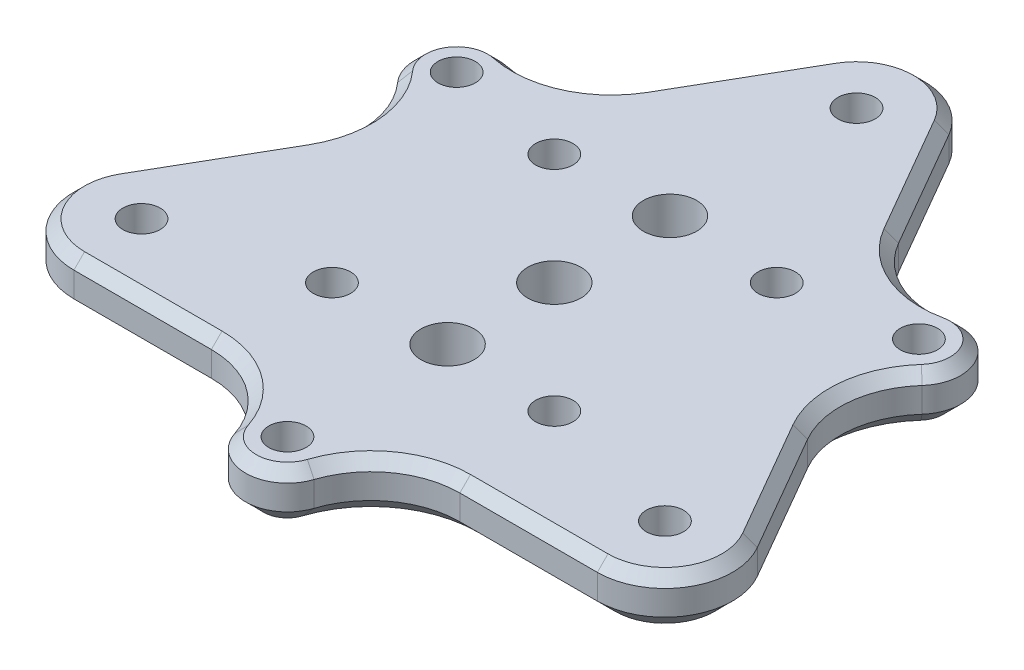
SolidWorks part; units mm, degrees
material "2014 合金"
ref_plane "正面" through (0, 0, 0) normal (0, 0, 1) x (1, 0, 0)
ref_plane "平面" through (0, 0, 0) normal (0, 1, 0) x (1, 0, 0)
ref_plane "右側面" through (0, 0, 0) normal (1, 0, 0) x (0, 0, -1)
sketch "ｽｹｯﾁ1" plane through (0, 0, 0) normal (0, 1, 0) x (1, 0, 0)
  line L1 (-28.3308, 10.9297) -> (-23.6409, 8.222)
  line L2 (4.7, -30) -> (4.7, -24.5846)
  line L3 (-23.6308, 19.0703) -> (-18.9409, 16.3626)
  line L4 (28.3308, 10.9297) -> (23.6409, 8.222)
  line L5 (-4.7, -30) -> (-4.7, -24.5846)
  line L8 (23.6308, 19.0703) -> (18.9409, 16.3626)
  line L17 (-36, -13.1846) -> (-6.5818, 37.7692)
  line L20 (29.4182, -24.5846) -> (-29.4182, -24.5846)
  line L23 (6.5818, 37.7692) -> (36, -13.1846)
  line L24 (36, -13.1846) -> (35.8926, -13.3525)
  circle A2 centre (25.9808, 15) radius 2.1
  circle A3 centre (-25.9808, 15) radius 2.1
  circle A4 centre (0, -30) radius 2.1
  circle A5 centre (29.4182, -16.9846) radius 7.6
  circle A6 centre (29.4182, -16.9846) radius 5
  circle A7 centre (-29.4182, -16.9846) radius 7.6
  circle A8 centre (25.9808, 15) radius 4.7
  circle A9 centre (-25.9808, 15) radius 4.7
  circle A10 centre (0, -30) radius 4.7
  circle A11 centre (-29.4182, -16.9846) radius 5
  circle A12 centre (0, 33.9692) radius 7.6
  circle A13 centre (0, 33.9692) radius 5
extrude "ﾎﾞｽ - 押し出し1" add sketch "ｽｹｯﾁ1" along normal blind 6 contours A12 L17 A7 L20 A5 L23 | A9 A3 | A9 L1 L17 L3 | A7 A11 | A10 L2 L20 L5 | A10 A4 | A5 A6 | A8 A2 | A8 L8 L23 L4 | A12 A13 region at (-23.559, 0, -10.8054) region at (-29.936, 0, -17.2835) region at (0, 0, 0) region at (-27.5068, 0, 9.8512) region at (0, 0, -41.3543) region at (0, 0, 24.6931) region at (0, 0, 25.4329) region at (21.3576, 0, -17.5922) region at (23.0226, 0, 13.2921) region at (28.2643, 0, -18.9552)
fillet "ﾌｨﾚｯﾄ1" radius 10 6 edges at (-23.6409, 3, -8.222) (-18.9409, 3, -16.3626) (18.9409, 3, -16.3626) (23.6409, 3, -8.222) (4.7, 3, 24.5846) (-4.7, 3, 24.5846)
chamfer "面取り1" distance 1.2 angle 45 18 edges at (36, 6, 20.7846) (21.6925, 6, 24.5846) (32.1371, 6, 6.494) (26.9878, 6, -6.227) (30.0511, 6, -17.35) (18.8866, 6, -20.2586) (10.4446, 6, -31.0786) (0, 6, -41.5692) (-10.4446, 6, -31.0786) (-18.8866, 6, -20.2586) (-30.0511, 6, -17.35) (-26.9878, 6, -6.227) (-32.1371, 6, 6.494) (-36, 6, 20.7846) (-21.6925, 6, 24.5846) (-8.1011, 6, 26.4856) (0, 6, 34.7) (8.1011, 6, 26.4856)
chamfer "面取り3" distance 2 angle 45 18 edges at (-18.8866, 0, -20.2586) (-10.4446, 0, -31.0786) (0, 0, -41.5692) (10.4446, 0, -31.0786) (18.8866, 0, -20.2586) (30.0511, 0, -17.35) (26.9878, 0, -6.227) (32.1371, 0, 6.494) (36, 0, 20.7846) (21.6925, 0, 24.5846) (8.1011, 0, 26.4856) (0, 0, 34.7) (-8.1011, 0, 26.4856) (-21.6925, 0, 24.5846) (-36, 0, 20.7846) (-32.1371, 0, 6.494) (-26.9878, 0, -6.227) (-30.0511, 0, -17.35)
sketch "ｽｹｯﾁ3" plane through (0, 0, 0) normal (0, -1, 0) x (1, 0, 0)
  circle A0 centre (0, 0) radius 3
extrude "ｶｯﾄ - 押し出し4" cut sketch "ｽｹｯﾁ3" against normal blind 15
sketch "ｽｹｯﾁ4" plane through (0, 0, 0) normal (0, -1, 0) x (1, 0, 0)
  circle A0 centre (0, 12.5) radius 3
  circle A1 centre (0, -12.5) radius 3
  circle A2 centre (-12.5, 12.5) radius 5
  circle A3 centre (12.5, 12.5) radius 5
  circle A4 centre (12.5, -12.5) radius 5
  circle A5 centre (-12.5, -12.5) radius 5
  circle A6 centre (-12.5, 12.5) radius 2.1
  circle A7 centre (12.5, 12.5) radius 2.1
  circle A8 centre (12.5, -12.5) radius 2.1
  circle A9 centre (-12.5, -12.5) radius 2.1
extrude "ｶｯﾄ - 押し出し9" cut sketch "ｽｹｯﾁ4" against normal blind 2 contours A4 | A5 | A2 | A3
sketch "ｽｹｯﾁ5" plane through (0, 2, 0) normal (0, -1, 0) x (1, 0, 0)
  circle A0 centre (12.5, 12.5) radius 2.1
  circle A1 centre (-12.5, 12.5) radius 2.1
  circle A2 centre (-12.5, -12.5) radius 2.1
  circle A3 centre (12.5, -12.5) radius 2.1
extrude "ｶｯﾄ - 押し出し11" cut sketch "ｽｹｯﾁ5" against normal up to next
sketch "ｽｹｯﾁ6" plane through (0, 0, 0) normal (0, -1, 0) x (-1, 0, 0)
  circle A0 centre (0, 13) radius 3
  circle A1 centre (0, -12) radius 3
extrude "ｶｯﾄ - 押し出し12" cut sketch "ｽｹｯﾁ6" against normal up to next
chamfer "面取り4" distance 0.25 angle 45 4 edges at (12.5, 0, 7.5) (12.5, 0, -17.5) (-12.5, 0, -17.5) (-12.5, 0, 7.5)
sketch "ｽｹｯﾁ8" plane through (0, 6, 0) normal (0, 1, 0) x (1, 0, 0)
  circle A0 centre (29.4182, -16.9846) radius 5
  circle A1 centre (29.4182, -16.9846) radius 2.1
extrude "ﾎﾞｽ - 押し出し4" add sketch "ｽｹｯﾁ8" against normal blind 4
sketch "ｽｹｯﾁ9" plane through (0, 6, 0) normal (0, 1, 0) x (1, 0, 0)
  circle A0 centre (0, 33.9692) radius 5
  circle A1 centre (0, 33.9692) radius 2.1
  circle A2 centre (-29.4182, -16.9846) radius 5
  circle A3 centre (-29.4182, -16.9846) radius 2.1
extrude "ﾎﾞｽ - 押し出し5" add sketch "ｽｹｯﾁ9" against normal blind 4
